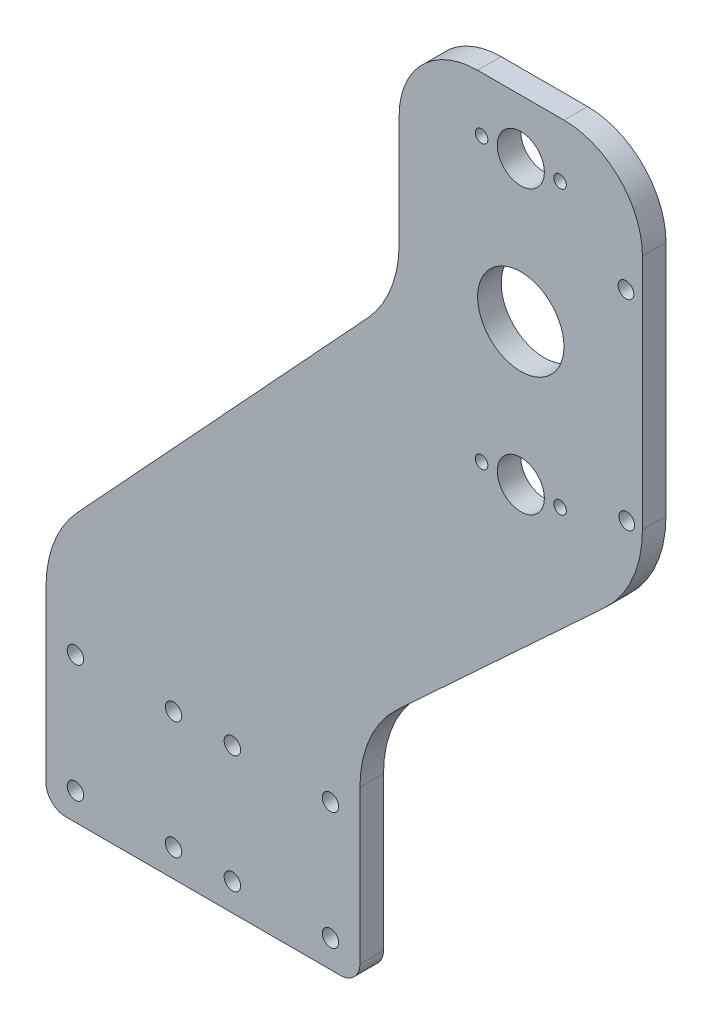
SolidWorks part; units mm, degrees
ref_plane "Front Plane" through (0, 0, 0) normal (0, 0, 1) x (1, 0, 0)
ref_plane "Top Plane" through (0, 0, 0) normal (0, 1, 0) x (1, 0, 0)
ref_plane "Right Plane" through (0, 0, 0) normal (1, 0, 0) x (0, 0, -1)
sketch "Sketch1" plane through (0, 0, 0) normal (0, 0, 1) x (1, 0, 0)
  line L0 (-23.4262, -99.1975) -> (-23.4262, -15.4242) construction
  line L1 (-58.4262, -99.1975) -> (11.5738, -99.1975)
  line L2 (-63.4262, -94.1975) -> (-63.4262, -50.9492)
  line L3 (-63.4262, -94.1975) -> (-23.4262, -94.1975) construction
  line L4 (16.5738, -94.1975) -> (16.5738, -55.2061)
  line L5 (46.5738, 118.0524) -> (68.5738, 118.0524)
  line L6 (26.5738, 98.0524) -> (26.5738, 69.804)
  line L7 (57.5738, 118.0524) -> (57.5738, 32.1124) construction
  line L8 (88.5738, 98.0524) -> (88.5738, 37.6266)
  line L9 (-43.4262, -77.1975) -> (-43.4262, -94.1975) construction
  line L10 (-55.9262, -62.1975) -> (-30.9262, -62.1975) construction
  line L11 (18.5918, 49.4274) -> (-55.4443, -30.5726)
  line L12 (78.945, 15.6036) -> (26.2025, -33.1831)
  line L13 (-55.9262, -62.1975) -> (-55.9262, -92.1975) construction
  line L14 (-55.9262, -92.1975) -> (-30.9262, -92.1975) construction
  line L15 (-30.9262, -62.1975) -> (-30.9262, -92.1975) construction
  line L16 (-55.9262, -62.1975) -> (-30.9262, -92.1975) construction
  line L17 (-55.9262, -92.1975) -> (-30.9262, -62.1975) construction
  line L18 (57.5738, 104.0524) -> (57.5738, 32.1124) construction
  arc A0 (78.945, 15.6036) -> (88.5738, 37.6266) centre (58.5738, 37.6266) ccw
  arc A1 (18.5918, 49.4274) -> (26.5738, 69.804) centre (-3.4262, 69.804) ccw
  arc A2 (16.5738, -55.2061) -> (26.2025, -33.1831) centre (46.5738, -55.2061) cw
  arc A3 (-63.4262, -50.9492) -> (-55.4443, -30.5726) centre (-33.4262, -50.9492) cw
  arc A4 (88.5738, 98.0524) -> (68.5738, 118.0524) centre (68.5738, 98.0524) ccw
  arc A5 (46.5738, 118.0524) -> (26.5738, 98.0524) centre (46.5738, 98.0524) ccw
  arc A6 (16.5738, -94.1975) -> (11.5738, -99.1975) centre (11.5738, -94.1975) cw
  arc A7 (-58.4262, -99.1975) -> (-63.4262, -94.1975) centre (-58.4262, -94.1975) cw
  circle A8 centre (-55.9262, -62.1975) radius 2.1
  circle A9 centre (-30.9262, -62.1975) radius 2.1
  circle A10 centre (-30.9262, -92.1975) radius 2.1
  circle A11 centre (-55.9262, -92.1975) radius 2.1
  circle A12 centre (9.0738, -92.1975) radius 2.1
  circle A13 centre (-15.9262, -92.1975) radius 2.1
  circle A14 centre (-15.9262, -62.1975) radius 2.1
  circle A15 centre (9.0738, -62.1975) radius 2.1
  circle A16 centre (57.5738, 104.0524) radius 6
  circle A17 centre (57.5738, 32.1124) radius 6
  circle A18 centre (57.5738, 68.0824) radius 11
  circle A19 centre (84.5738, 37.6266) radius 2
  circle A20 centre (84.3759, 88.5283) radius 2
  circle A21 centre (47.5738, 104.0524) radius 1.6
  circle A22 centre (47.5738, 32.1124) radius 1.6
  circle A23 centre (67.5738, 104.0524) radius 1.6
  circle A24 centre (67.5738, 32.1124) radius 1.6
  point P0 (0, 0)
  point P1 (57.5738, 82.2289)
  point P15 (26.5738, 58.0524)
  point P20 (-63.4262, -39.1975)
  point P23 (88.5738, 118.0524)
  point P26 (26.5738, 118.0524)
  point P29 (16.5738, -99.1975)
  point P32 (-63.4262, -99.1975)
  point P35 (-43.4262, -77.1975)
  dimension "D5" = 30
  dimension "D6" = 20
  dimension "D7" = 5
  dimension "D14" = 71.94
  dimension "D12" = 4
  dimension "D16" = 10
  dimension "D17" = 10
  dimension "D1" = 80
  dimension "D2" = 22
  dimension "D3" = 90
  dimension "D4" = 60
  dimension "D8" = 25
  dimension "D9" = 60
  dimension "D10" = 22
  dimension "D11" = 80
  dimension "D13" = 30
  dimension "D15" = 14
extrude "Boss-Extrude1" add sketch "Sketch1" along normal blind 6
